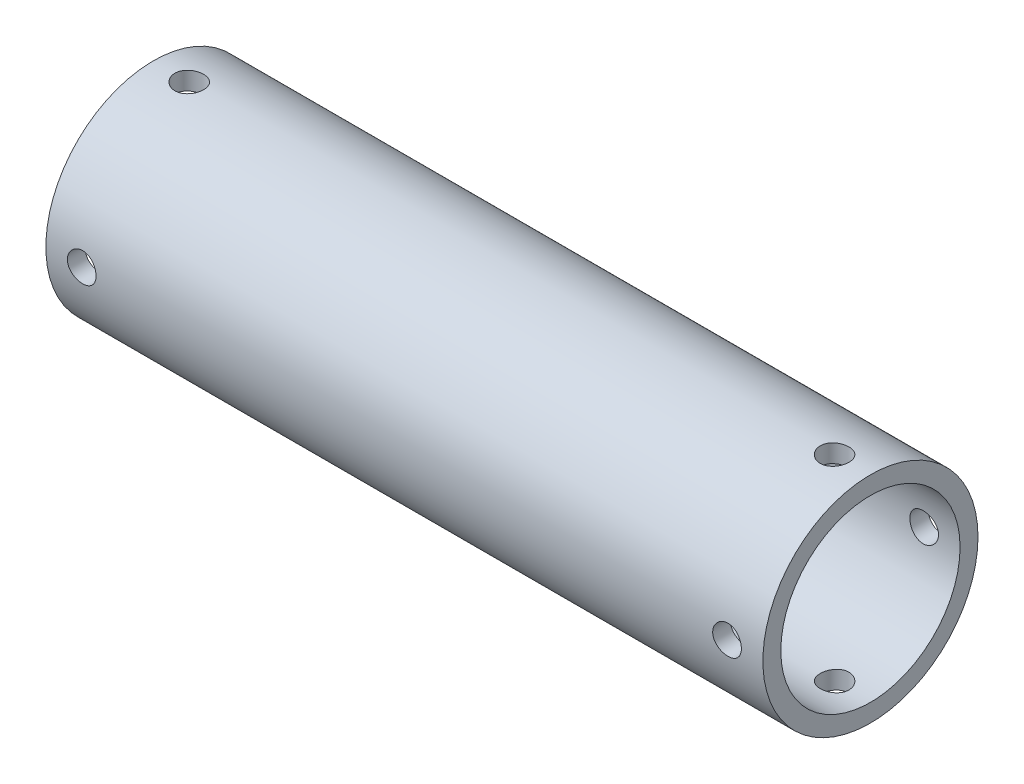
SolidWorks part; units mm, degrees
material "1060-H16"
ref_plane "Спереди" through (0, 0, 0) normal (0, 0, 1) x (1, 0, 0)
ref_plane "Сверху" through (0, 0, 0) normal (0, 1, 0) x (1, 0, 0)
ref_plane "Справа" through (0, 0, 0) normal (1, 0, 0) x (0, 0, -1)
other "Configuration Table"
sketch "Эскиз2" plane through (0, 0, 0) normal (1, 0, 0) x (0, 0, -1)
  circle A0 centre (0, 0) radius 30
  circle A1 centre (0, 0) radius 25
  dimension "D1" = 60
  dimension "D2" = 50
extrude "Бобышка-Вытянуть2" add sketch "Эскиз2" along normal blind 200
ref_plane "Плоскость1" through (0, 0, 25) normal (0, 0, 1) x (1, 0, 0)
sketch "Эскиз4" plane through (0, 0, 25) normal (0, 0, 1) x (1, 0, 0)
  line L0 (0, -30) -> (200, -30) construction
  line L1 (200, -30) -> (200, 30) construction
  circle A0 centre (10, 0) radius 4
  circle A1 centre (190, 0) radius 4
  dimension "D1" = 8
  dimension "D4" = 8
  dimension "D2" = 10
  dimension "D3" = 30
  dimension "D5" = 10
extrude "Вырез-Вытянуть2" cut sketch "Эскиз4" against normal blind 10 and the other way blind 10 contours A0 | A1
pattern_circular "Круговой массив1" count 4 over 360 about axis through (200, 0, 0) along (-1, 0, 0) of "Вырез-Вытянуть2"
equation "\"Diameter\"= 60мм"
equation "\"D1@Эскиз2\"= \"Diameter\""
equation "\"Length\"= 200мм"
equation "\"Thickness\"= 5мм"
equation "\"D1@Бобышка-Вытянуть2\"= \"Length\""
equation "\"D2@Эскиз2\" = \"Diameter\" - \"Thickness\" * 2"
equation "\"D4@Эскиз4\"=\"D1@Эскиз4\""
equation "\"D5@Эскиз4\"=\"D2@Эскиз4\""
equation "\"D3@Эскиз4\"=\"Diameter\"/2"
